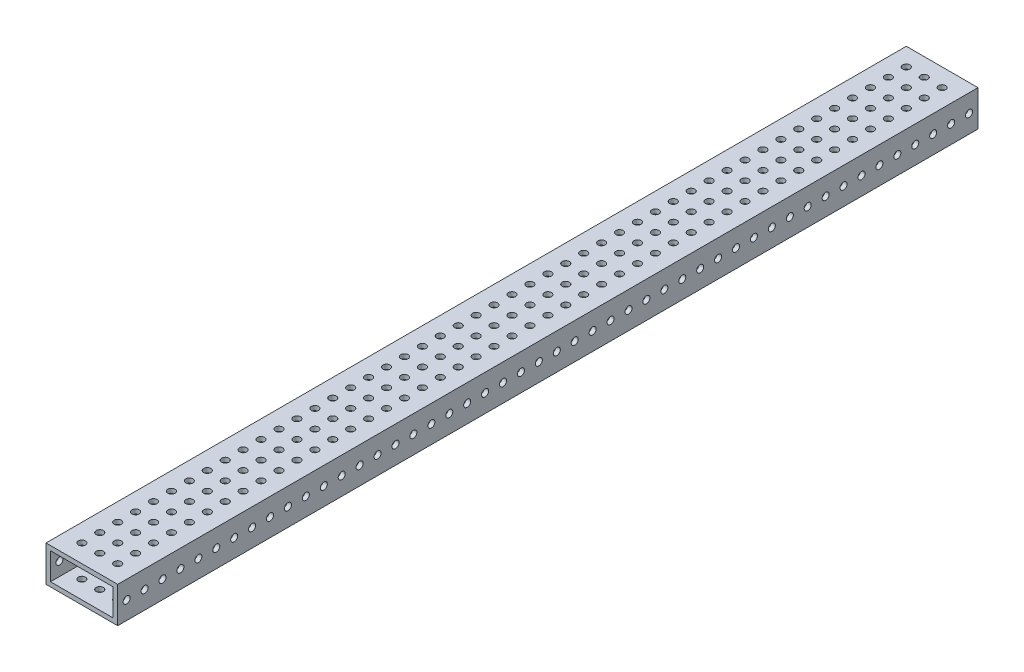
SolidWorks part; units mm, degrees
material "6061-T6 (SS)"
ref_plane "Front Plane" through (0, 0, 0) normal (0, 0, 1) x (1, 0, 0)
ref_plane "Top Plane" through (0, 0, 0) normal (0, 1, 0) x (1, 0, 0)
ref_plane "Right Plane" through (0, 0, 0) normal (1, 0, 0) x (0, 0, -1)
sketch "Sketch1" plane through (0, 0, 0) normal (0, 0, 1) x (1, 0, 0)
  line L0 (-22.225, 9.525) -> (22.225, 9.525)
  line L1 (-25.4, 12.7) -> (25.4, 12.7)
  line L2 (-25.4, 12.7) -> (-25.4, -12.7)
  line L3 (-25.4, -12.7) -> (25.4, -12.7)
  line L4 (25.4, 12.7) -> (25.4, -12.7)
  line L5 (22.225, 9.525) -> (22.225, -9.525)
  line L6 (-22.225, -9.525) -> (22.225, -9.525)
  line L7 (-22.225, 9.525) -> (-22.225, -9.525)
  line L8 (-25.4, 12.7) -> (25.4, -12.7) construction
  line L9 (25.4, 12.7) -> (-25.4, -12.7) construction
  point P5 (0, 0)
  dimension "D1" = 50.8
  dimension "D2" = 25.4
  dimension "D3" = 3.175
extrude "Boss-Extrude1" add sketch "Sketch1" along normal mid plane 609.6
sketch "Sketch2" plane through (0, 12.7, 0) normal (0, 1, 0) x (1, 0, 0)
  line L0 (25.4, -304.8) -> (-25.4, -304.8) construction
  line L1 (-25.4, -304.8) -> (-25.4, 304.8) construction
  line L2 (-12.7, -292.1) -> (0, -292.1) construction
  line L3 (0, -292.1) -> (12.7, -292.1) construction
  line L4 (25.4, 304.8) -> (-25.4, 304.8) construction
  circle A0 centre (0, -292.1) radius 2.5527
  circle A1 centre (12.7, -292.1) radius 2.5527
  circle A2 centre (-12.7, -292.1) radius 2.5527
  circle A3 centre (-12.7, -279.4) radius 2.5527
  circle A4 centre (0, -279.4) radius 2.5527
  circle A5 centre (12.7, -279.4) radius 2.5527
  circle A6 centre (-12.7, -266.7) radius 2.5527
  circle A7 centre (0, -266.7) radius 2.5527
  circle A8 centre (12.7, -266.7) radius 2.5527
  circle A9 centre (-12.7, -254) radius 2.5527
  circle A10 centre (0, -254) radius 2.5527
  circle A11 centre (12.7, -254) radius 2.5527
  circle A12 centre (-12.7, -241.3) radius 2.5527
  circle A13 centre (0, -241.3) radius 2.5527
  circle A14 centre (12.7, -241.3) radius 2.5527
  circle A15 centre (-12.7, -228.6) radius 2.5527
  circle A16 centre (0, -228.6) radius 2.5527
  circle A17 centre (12.7, -228.6) radius 2.5527
  circle A18 centre (-12.7, -215.9) radius 2.5527
  circle A19 centre (0, -215.9) radius 2.5527
  circle A20 centre (12.7, -215.9) radius 2.5527
  circle A21 centre (-12.7, -203.2) radius 2.5527
  circle A22 centre (0, -203.2) radius 2.5527
  circle A23 centre (12.7, -203.2) radius 2.5527
  circle A24 centre (-12.7, -190.5) radius 2.5527
  circle A25 centre (0, -190.5) radius 2.5527
  circle A26 centre (12.7, -190.5) radius 2.5527
  circle A27 centre (-12.7, -177.8) radius 2.5527
  circle A28 centre (0, -177.8) radius 2.5527
  circle A29 centre (12.7, -177.8) radius 2.5527
  circle A30 centre (-12.7, -165.1) radius 2.5527
  circle A31 centre (0, -165.1) radius 2.5527
  circle A32 centre (12.7, -165.1) radius 2.5527
  circle A33 centre (-12.7, -152.4) radius 2.5527
  circle A34 centre (0, -152.4) radius 2.5527
  circle A35 centre (12.7, -152.4) radius 2.5527
  circle A36 centre (-12.7, -139.7) radius 2.5527
  circle A37 centre (0, -139.7) radius 2.5527
  circle A38 centre (12.7, -139.7) radius 2.5527
  circle A39 centre (-12.7, -127) radius 2.5527
  circle A40 centre (0, -127) radius 2.5527
  circle A41 centre (12.7, -127) radius 2.5527
  circle A42 centre (-12.7, -114.3) radius 2.5527
  circle A43 centre (0, -114.3) radius 2.5527
  circle A44 centre (12.7, -114.3) radius 2.5527
  circle A45 centre (-12.7, -101.6) radius 2.5527
  circle A46 centre (0, -101.6) radius 2.5527
  circle A47 centre (12.7, -101.6) radius 2.5527
  circle A48 centre (-12.7, -88.9) radius 2.5527
  circle A49 centre (0, -88.9) radius 2.5527
  circle A50 centre (12.7, -88.9) radius 2.5527
  circle A51 centre (-12.7, -76.2) radius 2.5527
  circle A52 centre (0, -76.2) radius 2.5527
  circle A53 centre (12.7, -76.2) radius 2.5527
  circle A54 centre (-12.7, -63.5) radius 2.5527
  circle A55 centre (0, -63.5) radius 2.5527
  circle A56 centre (12.7, -63.5) radius 2.5527
  circle A57 centre (-12.7, -50.8) radius 2.5527
  circle A58 centre (0, -50.8) radius 2.5527
  circle A59 centre (12.7, -50.8) radius 2.5527
  circle A60 centre (-12.7, -38.1) radius 2.5527
  circle A61 centre (0, -38.1) radius 2.5527
  circle A62 centre (12.7, -38.1) radius 2.5527
  circle A63 centre (-12.7, -25.4) radius 2.5527
  circle A64 centre (0, -25.4) radius 2.5527
  circle A65 centre (12.7, -25.4) radius 2.5527
  circle A66 centre (-12.7, -12.7) radius 2.5527
  circle A67 centre (0, -12.7) radius 2.5527
  circle A68 centre (12.7, -12.7) radius 2.5527
  circle A69 centre (-12.7, 0) radius 2.5527
  circle A70 centre (0, 0) radius 2.5527
  circle A71 centre (12.7, 0) radius 2.5527
  circle A72 centre (-12.7, 12.7) radius 2.5527
  circle A73 centre (0, 12.7) radius 2.5527
  circle A74 centre (12.7, 12.7) radius 2.5527
  circle A75 centre (-12.7, 25.4) radius 2.5527
  circle A76 centre (0, 25.4) radius 2.5527
  circle A77 centre (12.7, 25.4) radius 2.5527
  circle A78 centre (-12.7, 38.1) radius 2.5527
  circle A79 centre (0, 38.1) radius 2.5527
  circle A80 centre (12.7, 38.1) radius 2.5527
  circle A81 centre (-12.7, 50.8) radius 2.5527
  circle A82 centre (0, 50.8) radius 2.5527
  circle A83 centre (12.7, 50.8) radius 2.5527
  circle A84 centre (-12.7, 63.5) radius 2.5527
  circle A85 centre (0, 63.5) radius 2.5527
  circle A86 centre (12.7, 63.5) radius 2.5527
  circle A87 centre (-12.7, 76.2) radius 2.5527
  circle A88 centre (0, 76.2) radius 2.5527
  circle A89 centre (12.7, 76.2) radius 2.5527
  circle A90 centre (-12.7, 88.9) radius 2.5527
  circle A91 centre (0, 88.9) radius 2.5527
  circle A92 centre (12.7, 88.9) radius 2.5527
  circle A93 centre (-12.7, 101.6) radius 2.5527
  circle A94 centre (0, 101.6) radius 2.5527
  circle A95 centre (12.7, 101.6) radius 2.5527
  circle A96 centre (-12.7, 114.3) radius 2.5527
  circle A97 centre (0, 114.3) radius 2.5527
  circle A98 centre (12.7, 114.3) radius 2.5527
  circle A99 centre (-12.7, 127) radius 2.5527
  circle A100 centre (0, 127) radius 2.5527
  circle A101 centre (12.7, 127) radius 2.5527
  circle A108 centre (-12.7, 152.4) radius 2.5527 [skipped]
  circle A109 centre (0, 152.4) radius 2.5527 [skipped]
  circle A110 centre (12.7, 152.4) radius 2.5527 [skipped]
  circle A111 centre (-12.7, 139.7) radius 2.5527 [skipped]
  circle A112 centre (0, 139.7) radius 2.5527 [skipped]
  circle A113 centre (12.7, 139.7) radius 2.5527 [skipped]
  circle A114 centre (12.7, 139.7) radius 2.5527
  circle A115 centre (0, 139.7) radius 2.5527
  circle A116 centre (-12.7, 139.7) radius 2.5527
  circle A117 centre (12.7, 152.4) radius 2.5527
  circle A118 centre (0, 152.4) radius 2.5527
  circle A119 centre (-12.7, 152.4) radius 2.5527
  circle A120 centre (12.7, 165.1) radius 2.5527
  circle A121 centre (0, 165.1) radius 2.5527
  circle A122 centre (-12.7, 165.1) radius 2.5527
  circle A123 centre (12.7, 177.8) radius 2.5527
  circle A124 centre (0, 177.8) radius 2.5527
  circle A125 centre (-12.7, 177.8) radius 2.5527
  circle A126 centre (12.7, 190.5) radius 2.5527
  circle A127 centre (0, 190.5) radius 2.5527
  circle A128 centre (-12.7, 190.5) radius 2.5527
  circle A129 centre (12.7, 203.2) radius 2.5527
  circle A130 centre (0, 203.2) radius 2.5527
  circle A131 centre (-12.7, 203.2) radius 2.5527
  circle A132 centre (12.7, 215.9) radius 2.5527
  circle A133 centre (0, 215.9) radius 2.5527
  circle A134 centre (-12.7, 215.9) radius 2.5527
  circle A135 centre (12.7, 228.6) radius 2.5527
  circle A136 centre (0, 228.6) radius 2.5527
  circle A137 centre (-12.7, 228.6) radius 2.5527
  circle A138 centre (12.7, 241.3) radius 2.5527
  circle A139 centre (0, 241.3) radius 2.5527
  circle A140 centre (-12.7, 241.3) radius 2.5527
  circle A141 centre (12.7, 254) radius 2.5527
  circle A142 centre (0, 254) radius 2.5527
  circle A143 centre (-12.7, 254) radius 2.5527
  circle A144 centre (12.7, 266.7) radius 2.5527
  circle A145 centre (0, 266.7) radius 2.5527
  circle A146 centre (-12.7, 266.7) radius 2.5527
  circle A147 centre (12.7, 279.4) radius 2.5527
  circle A148 centre (0, 279.4) radius 2.5527
  circle A149 centre (-12.7, 279.4) radius 2.5527
  circle A150 centre (12.7, 292.1) radius 2.5527
  circle A151 centre (0, 292.1) radius 2.5527
  circle A152 centre (-12.7, 292.1) radius 2.5527
  dimension "D2" = 5.1054
  dimension "D4" = 12.7
  dimension "D1" = 12.7
  dimension "D3" = 25.4
  dimension "D6" = 12.7
  dimension "D7" = 177.8
  dimension "D5" = 36
  dimension "D8" = 14
extrude "Cut-Extrude1" cut sketch "Sketch2" against normal through all
sketch "Sketch4" plane through (25.4, 0, 0) normal (1, 0, 0) x (0, 0, -1)
  line L1 (-304.8, -12.7) -> (-304.8, 12.7) construction
  line L2 (-304.8, -12.7) -> (304.8, -12.7) construction
  circle A2 centre (-298.45, 0) radius 2.4892
  circle A3 centre (-285.75, 0) radius 2.4892
  circle A16 centre (-273.05, 0) radius 2.4892
  circle A17 centre (-260.35, 0) radius 2.4892
  circle A18 centre (-247.65, 0) radius 2.4892
  circle A19 centre (133.35, 0) radius 2.4892
  circle A20 centre (146.05, 0) radius 2.4892
  circle A21 centre (158.75, 0) radius 2.4892
  circle A22 centre (171.45, 0) radius 2.4892
  circle A23 centre (184.15, 0) radius 2.4892
  circle A24 centre (196.85, 0) radius 2.4892
  circle A25 centre (209.55, 0) radius 2.4892
  circle A26 centre (222.25, 0) radius 2.4892
  circle A27 centre (234.95, 0) radius 2.4892
  circle A28 centre (247.65, 0) radius 2.4892
  circle A29 centre (260.35, 0) radius 2.4892
  circle A30 centre (273.05, 0) radius 2.4892
  circle A31 centre (285.75, 0) radius 2.4892
  circle A32 centre (298.45, 0) radius 2.4892
  circle A35 centre (-234.95, 0) radius 2.4892
  circle A36 centre (-222.25, 0) radius 2.4892
  circle A37 centre (-209.55, 0) radius 2.4892
  circle A38 centre (-196.85, 0) radius 2.4892
  circle A39 centre (-184.15, 0) radius 2.4892
  circle A40 centre (-171.45, 0) radius 2.4892
  circle A41 centre (-158.75, 0) radius 2.4892
  circle A42 centre (-146.05, 0) radius 2.4892
  circle A43 centre (-133.35, 0) radius 2.4892
  circle A44 centre (-120.65, 0) radius 2.4892
  circle A45 centre (-107.95, 0) radius 2.4892
  circle A46 centre (-95.25, 0) radius 2.4892
  circle A47 centre (-82.55, 0) radius 2.4892
  circle A48 centre (-69.85, 0) radius 2.4892
  circle A49 centre (-57.15, 0) radius 2.4892
  circle A50 centre (-44.45, 0) radius 2.4892
  circle A51 centre (-31.75, 0) radius 2.4892
  circle A52 centre (-19.05, 0) radius 2.4892
  circle A53 centre (-6.35, 0) radius 2.4892
  circle A54 centre (6.35, 0) radius 2.4892
  circle A55 centre (19.05, 0) radius 2.4892
  circle A56 centre (31.75, 0) radius 2.4892
  circle A57 centre (44.45, 0) radius 2.4892
  circle A58 centre (57.15, 0) radius 2.4892
  circle A59 centre (69.85, 0) radius 2.4892
  circle A60 centre (82.55, 0) radius 2.4892
  circle A61 centre (95.25, 0) radius 2.4892
  circle A62 centre (107.95, 0) radius 2.4892
  circle A63 centre (120.65, 0) radius 2.4892
  dimension "D2" = 4.9784
  dimension "D1" = 6.35
  dimension "D3" = 12.7
  dimension "D4" = 12.7
  dimension "D5" = 34
  dimension "D6" = 10
  dimension "D7" = 6
extrude "Cut-Extrude3" cut sketch "Sketch4" against normal through all
